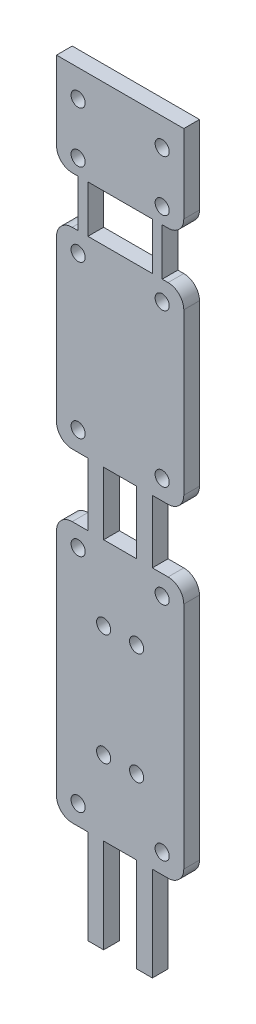
SolidWorks part; units mm, degrees
ref_plane "Front Plane" through (0, 0, 0) normal (0, 0, 1) x (1, 0, 0)
ref_plane "Top Plane" through (0, 0, 0) normal (0, 1, 0) x (1, 0, 0)
ref_plane "Right Plane" through (0, 0, 0) normal (1, 0, 0) x (0, 0, -1)
sketch "Sketch1" plane through (0, 0, 0) normal (0, 0, 1) x (1, 0, 0)
  line L0 (16.2, 1.5) -> (16.2, 14) construction
  line L1 (16.2, 109.64) -> (0, 109.64)
  line L2 (0, 109.64) -> (0, 99.66)
  line L3 (0, 1.5) -> (16.2, 1.5) construction
  line L4 (14.2, 59.21) -> (12.2, 59.21)
  line L5 (0, 14) -> (4, 14) construction
  line L6 (2, 26) -> (4, 26)
  line L7 (2, 91.66) -> (2.75, 91.66)
  line L8 (2, 67.21) -> (4, 67.21)
  line L9 (8.1, 109.64) -> (8.1, 97.66) construction
  line L10 (0, 14) -> (0, 1.5) construction
  line L11 (2, 97.66) -> (2.75, 97.66)
  line L12 (16.2, 28) -> (16.2, 57.21)
  line L13 (16.2, 99.66) -> (16.2, 109.64)
  line L14 (0, 89.66) -> (0, 69.21)
  line L15 (0, 57.21) -> (0, 28)
  line L16 (16.2, 69.21) -> (16.2, 89.66)
  line L17 (6, 14) -> (6, 26)
  line L18 (4, 59.21) -> (4, 67.21)
  line L19 (4, 14) -> (4, 26)
  line L20 (6, 59.21) -> (6, 67.21)
  line L21 (4, 91.66) -> (4, 97.66)
  line L22 (2.75, 97.66) -> (2.75, 91.66)
  line L23 (10.2, 14) -> (10.2, 26)
  line L24 (12.2, 14) -> (12.2, 26)
  line L25 (10.2, 59.21) -> (10.2, 67.21)
  line L26 (12.2, 59.21) -> (12.2, 67.21)
  line L27 (13.45, 91.66) -> (13.45, 97.66)
  line L28 (12.2, 91.66) -> (12.2, 97.66)
  line L29 (4, 97.66) -> (12.2, 97.66)
  line L30 (4, 91.66) -> (12.2, 91.66)
  line L31 (13.45, 91.66) -> (14.2, 91.66)
  line L32 (13.45, 97.66) -> (14.2, 97.66)
  line L33 (6, 67.21) -> (10.2, 67.21)
  line L34 (12.2, 67.21) -> (14.2, 67.21)
  line L35 (10.2, 59.21) -> (6, 59.21)
  line L36 (4, 59.21) -> (2, 59.21)
  line L37 (6, 14) -> (10.2, 14) construction
  line L38 (6, 26) -> (10.2, 26)
  line L39 (12.2, 26) -> (14.2, 26)
  line L40 (12.2, 14) -> (16.2, 14) construction
  line L41 (12.2, 14) -> (10.2, 14)
  line L42 (6, 14) -> (4, 14)
  circle A0 centre (13.45, 56.71) radius 0.9
  circle A1 centre (10.2, 49.71) radius 0.9
  circle A2 centre (13.45, 106.16) radius 0.9
  circle A3 centre (2.75, 99.66) radius 0.9
  circle A4 centre (6, 49.71) radius 0.9
  circle A5 centre (2.75, 28.5) radius 0.9
  circle A6 centre (2.75, 89.16) radius 0.9
  circle A7 centre (2.75, 56.71) radius 0.9
  circle A8 centre (13.45, 89.16) radius 0.9
  circle A9 centre (13.45, 99.66) radius 0.9
  arc A10 (16.2, 28) -> (14.2, 26) centre (14.2, 28) cw
  arc A11 (0, 28) -> (2, 26) centre (2, 28) ccw
  arc A12 (16.2, 57.21) -> (14.2, 59.21) centre (14.2, 57.21) ccw
  arc A13 (0, 57.21) -> (2, 59.21) centre (2, 57.21) cw
  arc A14 (16.2, 69.21) -> (14.2, 67.21) centre (14.2, 69.21) cw
  arc A15 (0, 69.21) -> (2, 67.21) centre (2, 69.21) ccw
  arc A16 (0, 89.66) -> (2, 91.66) centre (2, 89.66) cw
  arc A17 (16.2, 89.66) -> (14.2, 91.66) centre (14.2, 89.66) ccw
  arc A18 (16.2, 99.66) -> (14.2, 97.66) centre (14.2, 99.66) cw
  arc A19 (2, 97.66) -> (0, 99.66) centre (2, 99.66) cw
  circle A28 centre (13.45, 69.71) radius 0.9
  circle A29 centre (6, 35.5) radius 0.9
  circle A32 centre (2.75, 106.16) radius 0.9
  circle A33 centre (10.2, 35.5) radius 0.9
  circle A34 centre (2.75, 69.71) radius 0.9
  circle A35 centre (13.45, 28.5) radius 0.9
  circle A36 centre (2.85, 11.5) radius 0.9 construction
  circle A37 centre (13.35, 11.5) radius 0.9 construction
  circle A38 centre (13.35, 5.5) radius 0.9 construction
  circle A39 centre (2.85, 5.5) radius 0.9 construction
  point P71 (16.2, 26)
  point P74 (0, 26)
  point P91 (16.2, 59.21)
  point P94 (0, 59.21)
  point P97 (16.2, 67.21)
  point P100 (0, 67.21)
  point P103 (0, 91.66)
  point P106 (16.2, 91.66)
  point P109 (16.2, 97.66)
  point P112 (0, 97.66)
  dimension "D45" = 1.8
  dimension "D46" = 2
  dimension "D1" = 4
  dimension "D2" = 4
  dimension "D3" = 2.85
  dimension "D4" = 2.85
  dimension "D5" = 16.2
  dimension "D6" = 6
  dimension "D7" = 6
  dimension "D8" = 2.85
  dimension "D9" = 2.85
  dimension "D10" = 2.5
  dimension "D11" = 12
  dimension "D12" = 33.21
  dimension "D13" = 2.5
  dimension "D14" = 2.5
  dimension "D15" = 2.75
  dimension "D16" = 2.75
  dimension "D17" = 2.5
  dimension "D18" = 2.5
  dimension "D19" = 2.75
  dimension "D20" = 2.75
  dimension "D21" = 9.5
  dimension "D22" = 6
  dimension "D23" = 9.5
  dimension "D24" = 6
  dimension "D25" = 9.5
  dimension "D26" = 9.5
  dimension "D27" = 6
  dimension "D28" = 6
  dimension "D29" = 8
  dimension "D30" = 24.45
  dimension "D31" = 2.5
  dimension "D32" = 2.5
  dimension "D33" = 2.75
  dimension "D34" = 2.75
  dimension "D35" = 6
  dimension "D36" = 2.75
  dimension "D37" = 2
  dimension "D38" = 2.75
  dimension "D39" = 8.5
  dimension "D40" = 11.98
  dimension "D41" = 2.5
  dimension "D42" = 2.5
  dimension "D43" = 2.75
  dimension "D44" = 2.75
extrude "Boss-Extrude1" add sketch "Sketch1" along normal blind 2
sketch "Sketch2" plane through (0, 0, 0) normal (0, 0, -1) x (-1, 0, 0)
  line L0 (-13.45, 97.66) -> (-2.75, 97.66)
  line L1 (-2.75, 97.66) -> (-2.75, 91.66)
  line L2 (-2.75, 91.66) -> (-13.45, 91.66)
  line L3 (-13.45, 91.66) -> (-13.45, 97.66)
  line L4 (-12.2, 67.21) -> (-4, 67.21)
  line L5 (-4, 67.21) -> (-4, 59.21)
  line L6 (-4, 59.21) -> (-12.2, 59.21)
  line L7 (-12.2, 59.21) -> (-12.2, 67.21)
  line L8 (-12.2, 26) -> (-4, 26)
  line L9 (-4, 26) -> (-4, 14)
  line L10 (-4, 14) -> (-12.2, 14)
  line L11 (-12.2, 14) -> (-12.2, 26)
extrude "Cut-Extrude1" [suppressed] cut sketch "Sketch2" against normal up to surface (2 mm away) up to face at (3.65, 69.71, 2)
equation "\"D12@Sketch1\"= \"HL@parametersSketch@prostheticParameters.SLDPRT\" * 0.266 - 12 - 4 'Middle PIP Length"
equation "\"D30@Sketch1\"= \"HL@parametersSketch@prostheticParameters.SLDPRT\" * 0.17 - 4 - 3'Middle MIP Length"
equation "\"D5@Sketch1\"= \"fingerWidth@parametersSketch@prostheticParameters.SLDPRT\" 'Middle Width"
equation "\"D40@Sketch1\"= \"HL@parametersSketch@prostheticParameters.SLDPRT\" * 0.108 - 3 - 5'Middle DIP Length"
equation "\"D45@Sketch1\"= 1.5 + \"tol1@parametersSketch@prostheticParameters.SLDPRT\""
